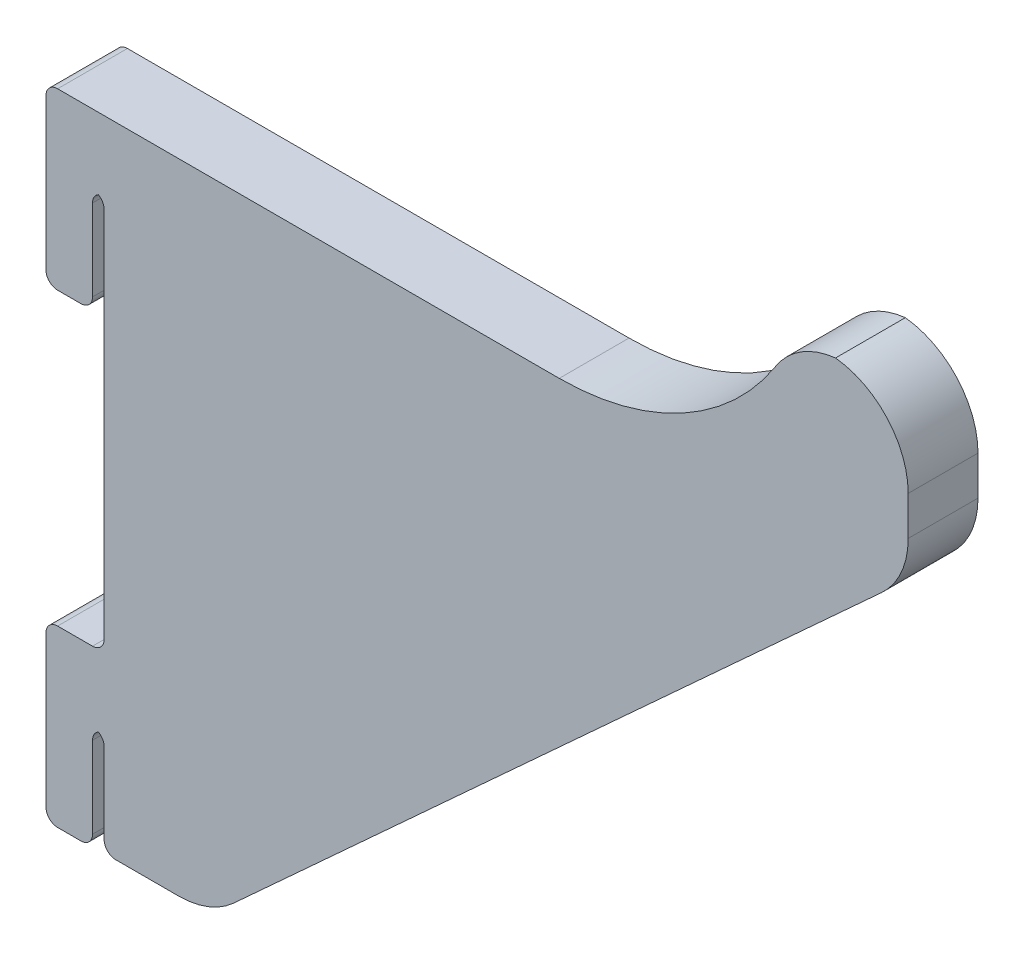
SolidWorks part; units mm, degrees
ref_plane "Plan de face" through (0, 0, 0) normal (0, 0, 1) x (1, 0, 0)
ref_plane "Plan de dessus" through (0, 0, 0) normal (0, 1, 0) x (1, 0, 0)
ref_plane "Plan de droite" through (0, 0, 0) normal (1, 0, 0) x (0, 0, -1)
sketch "Esquisse1" plane through (0, 0, 0) normal (0, 0, 1) x (1, 0, 0)
  line L0 (0, 0) -> (0, 9)
  line L1 (0, 9) -> (1, 9)
  line L4 (1, 0.0964) -> (10.1219, 0.0964)
  line L8 (10.1219, 55) -> (-4, 55)
  line L9 (1, 49) -> (0, 49)
  line L10 (0, 0) -> (-4, 0)
  line L11 (-4, 0) -> (-4, 15)
  line L12 (-4, 15) -> (1, 15)
  line L13 (1, 15) -> (1, 49)
  line L14 (0, 49) -> (0, 40)
  line L15 (0, 40) -> (-4, 40)
  line L16 (-4, 40) -> (-4, 55)
  line L17 (1, 9) -> (1, 0.0964)
  line L18 (10.1219, 55) -> (70.1219, 55) construction
  line L19 (10.1219, 55) -> (19.2932, 55)
  line L21 (60.4324, 68.4362) -> (70.1219, 68.4362)
  line L22 (70.1219, 68.4362) -> (70.1219, 55)
  line L23 (70.1219, 55) -> (10.1219, 0.0964)
  line L25 (40.1219, 55) -> (19.2932, 55)
  arc A1 (40.1219, 55) -> (60.4324, 68.4362) centre (40.1219, 77.0691) ccw
  point P11 (0.5, 9)
  dimension "D1" = 40
  dimension "D2" = 1
  dimension "D3" = 1
  dimension "D4" = 15
  dimension "D5" = 15
  dimension "D6" = 4
  dimension "D7" = 4
  dimension "D8" = 6
  dimension "D9" = 6
  dimension "D10" = 60
extrude "Boss.-Extru.1" add sketch "Esquisse1" along normal blind 6
fillet "Congé3" radius 1 12 edges at (1, 0.0964, 3) (1, 9, 3) (0, 9, 3) (0, 0, 3) (-4, 0, 3) (-4, 15, 3) (1, 15, 3) (0, 40, 3) (-4, 40, 3) (-4, 55, 3) (1, 49, 3) (0, 49, 3)
fillet "Congé4" radius 7 4 edges at (10.1219, 0.0964, 3) (70.1219, 55, 3) (70.1219, 68.4362, 3) (60.4324, 68.4362, 3)
